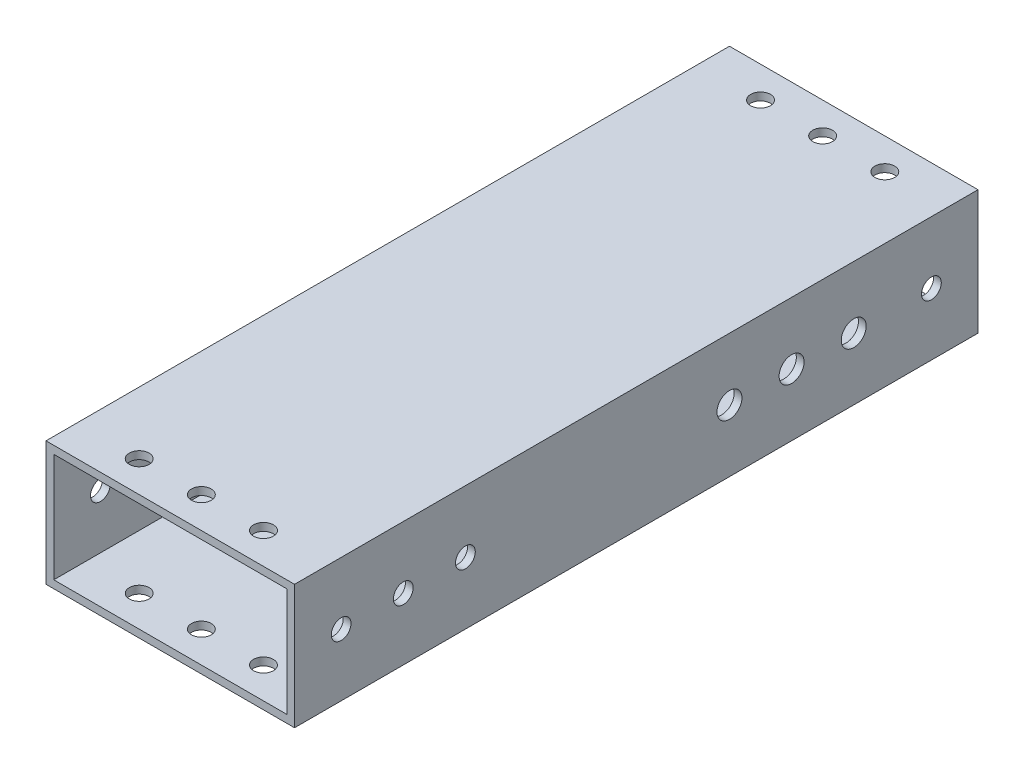
SolidWorks part; units mm, degrees
material "6061-T6 (SS)"
ref_plane "Front Plane" through (0, 0, 0) normal (0, 0, 1) x (1, 0, 0)
ref_plane "Top Plane" through (0, 0, 0) normal (0, 1, 0) x (1, 0, 0)
ref_plane "Right Plane" through (0, 0, 0) normal (1, 0, 0) x (0, 0, -1)
sketch "Sketch1" plane through (0, 0, 0) normal (0, 0, 1) x (1, 0, 0)
  line L0 (-23.8125, 11.1125) -> (23.8125, 11.1125)
  line L1 (-25.4, -12.7) -> (25.4, -12.7)
  line L2 (-25.4, -12.7) -> (-25.4, 12.7)
  line L3 (-25.4, 12.7) -> (25.4, 12.7)
  line L4 (25.4, -12.7) -> (25.4, 12.7)
  line L5 (-25.4, -12.7) -> (25.4, 12.7) construction
  line L6 (-25.4, 12.7) -> (25.4, -12.7) construction
  line L7 (23.8125, -11.1125) -> (23.8125, 11.1125)
  line L8 (-23.8125, -11.1125) -> (23.8125, -11.1125)
  line L9 (-23.8125, -11.1125) -> (-23.8125, 11.1125)
  point P0 (0, 0)
  dimension "D1" = 50.8
  dimension "D2" = 25.4
  dimension "D3" = 1.5875
extrude "Boss-Extrude1" add sketch "Sketch1" along normal mid plane 139.7
sketch "Sketch2" plane through (0, 12.7, 0) normal (0, 1, 0) x (1, 0, 0)
  line L0 (25.4, 69.85) -> (-25.4, 69.85) construction
  line L1 (25.4, 0) -> (-25.4, 0) construction
  line L2 (25.4, -69.85) -> (25.4, 69.85) construction
  line L3 (-25.4, -69.85) -> (-25.4, 69.85) construction
  circle A0 centre (-12.7, 63.5) radius 2.0193
  circle A1 centre (0, 63.5) radius 2.0193
  circle A2 centre (12.7, 63.5) radius 2.0193
  circle A3 centre (12.7, -63.5) radius 2.0193
  circle A4 centre (0, -63.5) radius 2.0193
  circle A5 centre (-12.7, -63.5) radius 2.0193
  dimension "D4" = 4.0386
  dimension "D1" = 12.7
  dimension "D2" = 12.7
  dimension "D3" = 6.35
extrude "Cut-Extrude1" cut sketch "Sketch2" against normal through all
sketch "Sketch3" plane through (-25.4, 0, 0) normal (-1, 0, 0) x (0, 0, 1)
  line L0 (-69.85, 12.7) -> (-69.85, -12.7) construction
  line L1 (0, 12.7) -> (0, -12.7) construction
  line L2 (69.85, 12.7) -> (-69.85, 12.7) construction
  line L3 (69.85, -12.7) -> (-69.85, -12.7) construction
  circle A0 centre (-60.325, 0) radius 2.0193
  circle A1 centre (60.325, 0) radius 2.0193
  circle A4 centre (34.925, 0) radius 2.0193
  circle A5 centre (47.625, 0) radius 2.0193
  dimension "D1" = 4.0386
  dimension "D3" = 12.7
  dimension "D4" = 12.7
  dimension "D2" = 9.525
extrude "Cut-Extrude2" cut sketch "Sketch3" against normal through all contours A5 | A1 | A4 | A0
sketch "Sketch5" plane through (25.4, 0, 0) normal (1, 0, 0) x (0, 0, -1)
  line L0 (69.85, -12.7) -> (69.85, 12.7) construction
  circle A0 centre (31.75, 0) radius 2.5527
  circle A1 centre (44.45, 0) radius 2.5527
  circle A2 centre (19.05, 0) radius 2.5527
  dimension "D1" = 12.7
  dimension "D2" = 12.7
  dimension "D3" = 5.1054
  dimension "D4" = 38.1
extrude "Cut-Extrude3" cut sketch "Sketch5" against normal through all
